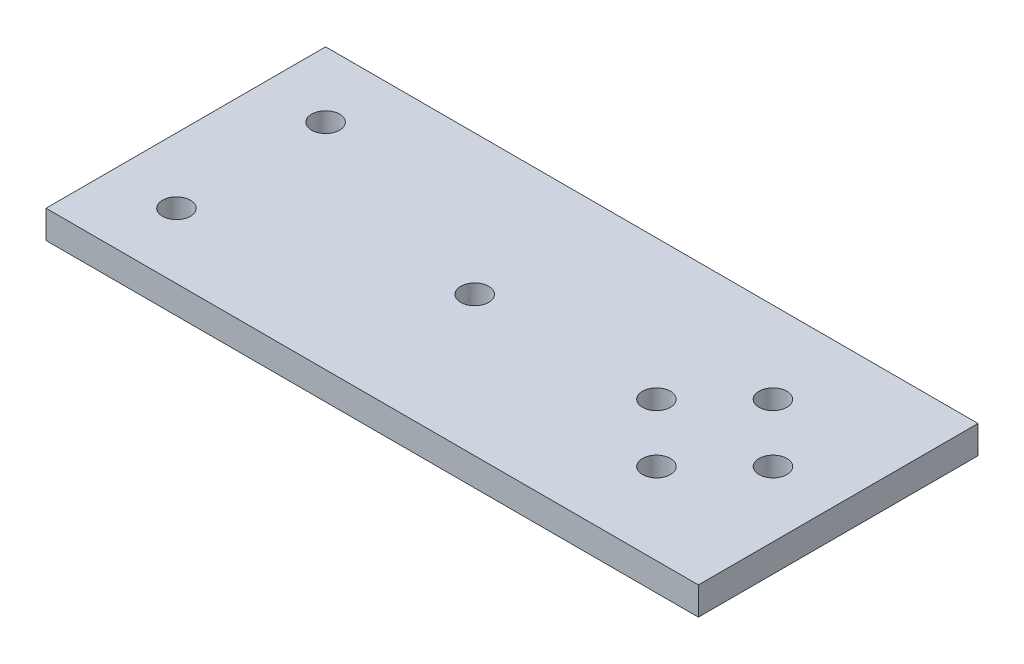
SolidWorks part; units mm, degrees
ref_plane "Płaszczyzna przednia" through (0, 0, 0) normal (0, 0, 1) x (1, 0, 0)
ref_plane "Płaszczyzna górna" through (0, 0, 0) normal (0, 1, 0) x (1, 0, 0)
ref_plane "Płaszczyzna prawa" through (0, 0, 0) normal (1, 0, 0) x (0, 0, -1)
sketch "Szkic1" plane through (0, 0, 0) normal (0, 1, 0) x (1, 0, 0)
  line L1 (-35, 15) -> (35, 15)
  line L2 (-35, 15) -> (-35, -15)
  line L3 (-35, -15) -> (35, -15)
  line L4 (35, 15) -> (35, -15)
  line L5 (-35, 15) -> (35, -15) construction
  line L6 (-35, -15) -> (35, 15) construction
  point P0 (0, 0)
  dimension "D1" = 30
  dimension "D2" = 70
base flange "Odgięcie bazowe1" sketch "Szkic1" thickness 3 reverse thickness direction no parameters "D1"=0.7366
sketch "Szkic6" plane through (0, 0, 0) normal (0, 1, 0) x (1, 0, 0)
  line L0 (35, 15) -> (-35, 15) construction
  line L1 (-35, 15) -> (-35, -15) construction
  circle A1 centre (-28, 8) radius 1.5
  dimension "D1" = 3
  dimension "D2" = 7
  dimension "D3" = 7
extrude "Wytnij-wyciągnięcie1" cut sketch "Szkic6" against normal up to next normal cut yes
mirror "Lustro1" about plane through (0, 0, 0) normal (0, 0, 1) of "Wytnij-wyciągnięcie1"
sketch "Szkic7" plane through (0, 0, 0) normal (0, 1, 0) x (1, 0, 0)
  line L0 (-35, 15) -> (-35, -15) construction
  line L1 (35, -15) -> (35, 15) construction
  circle A0 centre (28, 0) radius 1.5
  point P5 (-35, 0)
  dimension "D1" = 3
  dimension "D2" = 7
extrude "Wytnij-wyciągnięcie2" cut sketch "Szkic7" against normal up to next normal cut yes
sketch "Szkic8" plane through (0, 0, 0) normal (0, 1, 0) x (1, 0, 0)
  line L0 (33.5005, 0) -> (11.1476, 0) construction
  line L1 (21.75, 7.7998) -> (21.75, -7.9538) construction
  point P0 (28, 0)
  point P1 (15.5, 0)
  point P3 (21.75, 6.25)
  point P4 (21.75, -6.25)
  dimension "D1" = 12.5
  dimension "D2" = 12.5
pattern_sketch "Szkic-szyk1" of "Wytnij-wyciągnięcie2" driven by "Szkic8"
sketch "Szkic9" plane through (0, 0, 0) normal (0, 1, 0) x (1, 0, 0)
  line L0 (35.0288, 0) -> (-39.9895, 0) construction
  line L1 (21.75, -7.75) -> (21.75, 7.75) construction
  circle A0 centre (21.75, -6.25) radius 1.5 construction
  circle A1 centre (21.75, 6.25) radius 1.5 construction
  point P10 (21.75, 0)
sketch "Szkic10" plane through (0, 0, 0) normal (0, 1, 0) x (1, 0, 0)
  line L0 (35.0288, 0) -> (-39.9895, 0) construction
  line L1 (-35, 15) -> (-35, -15) construction
  circle A0 centre (-4, 0) radius 1.5
  dimension "D1" = 3
  dimension "D2" = 31
extrude "Wytnij-wyciągnięcie3" cut sketch "Szkic10" against normal up to next normal cut yes
sketch "Linie zgięcia1" [suppressed] plane through (0, 0, 0) normal (0, 1, 0) x (1, 0, 0)
sketch "Ramka-graniczna1" [suppressed] plane through (0, 0, 0) normal (0, 1, 0) x (1, 0, 0)
sheet metal parameters "Arkusz blachy1" thickness 3 parameters "D1"=0.7366
flat pattern "Rozłożony model1" [suppressed]
sketch "Linie zgięcia2" plane through (0, 0, 0) normal (0, 1, 0) x (1, 0, 0)
sketch3d "Ramka-graniczna2" [suppressed]
  line L0 (-35, -15, 0) -> (35, -15, 0) construction
  line L1 (-35, 15, 0) -> (35, 15, 0) construction
  line L2 (-35, -15, 0) -> (-35, 15, 0) construction
  line L3 (35, -15, 0) -> (35, 15, 0) construction
sheet metal parameters "Arkusz blachy2" thickness 3 parameters "D1"=0.7366
flat pattern "Rozłożony model1"
sketch "Linie zgięcia2" plane through (0, 0, 0) normal (0, 1, 0) x (1, 0, 0)
sketch3d "Ramka-graniczna2" [suppressed]
  line L0 (35, -15, 0) -> (-35, -15, 0) construction
  line L1 (35, 15, 0) -> (-35, 15, 0) construction
  line L2 (35, -15, 0) -> (35, 15, 0) construction
  line L3 (-35, -15, 0) -> (-35, 15, 0) construction
sheet metal parameters "Arkusz blachy3" thickness 3 parameters "D1"=0.7366
flat pattern "Rozłożony model1"
sketch "Linie zgięcia2" plane through (0, 0, 0) normal (0, 1, 0) x (1, 0, 0)
sketch3d "Ramka-graniczna2" [suppressed]
  line L0 (35, -15, 0) -> (-35, -15, 0) construction
  line L1 (35, 15, 0) -> (-35, 15, 0) construction
  line L2 (35, -15, 0) -> (35, 15, 0) construction
  line L3 (-35, -15, 0) -> (-35, 15, 0) construction
sheet metal parameters "Arkusz blachy4" thickness 3 parameters "D1"=0.7366
flat pattern "Rozłożony model1"
sketch "Linie zgięcia2" plane through (0, 0, 0) normal (0, 1, 0) x (1, 0, 0)
sketch3d "Ramka-graniczna2" [suppressed]
  line L0 (35, -15, 0) -> (-35, -15, 0) construction
  line L1 (35, 15, 0) -> (-35, 15, 0) construction
  line L2 (35, -15, 0) -> (35, 15, 0) construction
  line L3 (-35, -15, 0) -> (-35, 15, 0) construction
sheet metal parameters "Arkusz blachy5" thickness 3 parameters "D1"=0.7366
flat pattern "Rozłożony model1"
sketch "Linie zgięcia2" plane through (0, 0, 0) normal (0, 1, 0) x (1, 0, 0)
sketch3d "Ramka-graniczna2" [suppressed]
  line L0 (35, -15, 0) -> (-35, -15, 0) construction
  line L1 (35, 15, 0) -> (-35, 15, 0) construction
  line L2 (35, -15, 0) -> (35, 15, 0) construction
  line L3 (-35, -15, 0) -> (-35, 15, 0) construction
sheet metal parameters "Arkusz blachy6" thickness 3 parameters "D1"=0.7366
flat pattern "Rozłożony model1"
sketch "Linie zgięcia2" plane through (0, 0, 0) normal (0, 1, 0) x (1, 0, 0)
sketch3d "Ramka-graniczna2" [suppressed]
  line L0 (35, -15, 0) -> (-35, -15, 0) construction
  line L1 (35, 15, 0) -> (-35, 15, 0) construction
  line L2 (35, -15, 0) -> (35, 15, 0) construction
  line L3 (-35, -15, 0) -> (-35, 15, 0) construction
